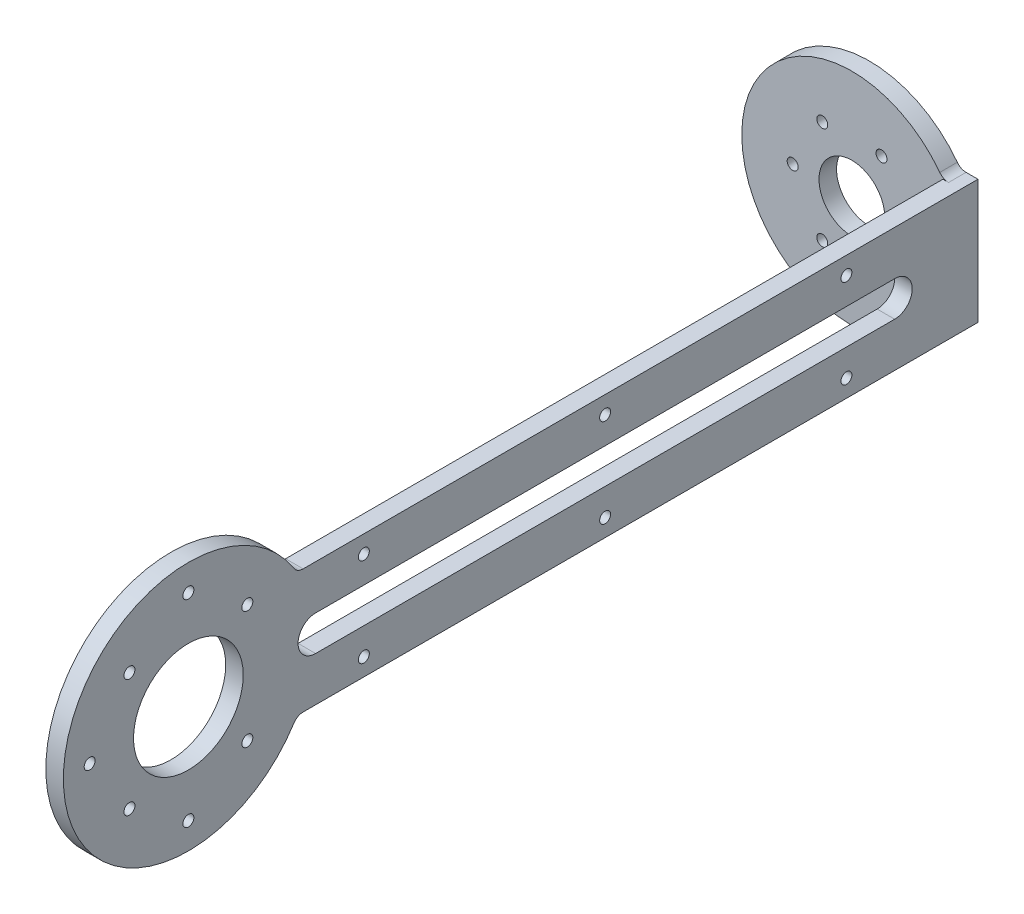
SolidWorks part; units mm, degrees
material "AISI 304"
ref_plane "前视基准面" through (0, 0, 0) normal (0, 0, 1) x (1, 0, 0)
ref_plane "上视基准面" through (0, 0, 0) normal (0, 1, 0) x (1, 0, 0)
ref_plane "右视基准面" through (0, 0, 0) normal (1, 0, 0) x (0, 0, -1)
other "Configuration Table"
sketch "草图1" plane through (0, 0, 0) normal (0, 0, 1) x (1, 0, 0)
  circle A0 centre (0, 0) radius 28.5
  dimension "D1" = 57
extrude "凸台-拉伸1" add sketch "草图1" along normal blind 4
sketch "草图2" plane through (0, 0, 4) normal (0, 0, 1) x (1, 0, 0)
  circle A0 centre (-13.5, 0) radius 1.25
  circle A1 centre (-6.75, 11.6913) radius 1.25
  circle A2 centre (6.75, 11.6913) radius 1.25
  circle A4 centre (6.75, -11.6913) radius 1.25
  circle A5 centre (-6.75, -11.6913) radius 1.25
  circle A6 centre (13.5, 0) radius 1.25 [skipped]
  point P16 (0, 0)
  dimension "D1" = 2.5
  dimension "D2" = 13.5
  dimension "D3" = 6
extrude "切除-拉伸2" cut sketch "草图2" against normal blind 4
sketch "草图4" plane through (0, 0, 4) normal (0, 0, 1) x (1, 0, 0)
  line L0 (-23.5601, 0) -> (35.9278, 0) construction
  line L1 (20.75, 14.1311) -> (20.75, -14.1311)
  line L2 (24.75, 14.1311) -> (24.75, -14.1311)
  line L3 (24.75, 14.1311) -> (20.75, 14.1311)
  line L4 (24.75, -14.1311) -> (20.75, -14.1311)
  circle A0 centre (0, 0) radius 28.5 construction
  circle A1 centre (6.75, 11.6913) radius 1.25 construction
  circle A2 centre (0, 0) radius 28.5
  circle A3 centre (6.75, 11.6913) radius 1.25
  arc A4 (20.75, 14.1311) -> (20.75, -14.1311) centre (0, 0) ccw
  circle M13 centre (0, 0) radius 28.5
  dimension "D1" = 14
  dimension "D2" = 4
extrude "切除-拉伸4" cut sketch "草图4" against normal blind 4 contours A4 L3 L4 M13 | L2 L0 A2 | L0 L2 M13 region at (26.2588, 5.349, 4) region at (26.2588, -5.349, 4) region at (-25.8848, 0, 4)
sketch "草图5" plane through (0, 0, 4) normal (0, 0, 1) x (1, 0, 0)
  circle A0 centre (0, 0) radius 7.5
  dimension "D1" = 15
extrude "切除-拉伸5" cut sketch "草图5" against normal blind 4
sketch "草图6" plane through (0, 0, 4) normal (0, 0, 1) x (1, 0, 0)
  line L0 (-22.1913, 0) -> (33.046, 0) construction
  line L1 (20.75, 14.1311) -> (24.75, 14.1311)
  line L2 (24.75, 14.1311) -> (24.75, -14.1311)
  line L3 (24.75, -14.1311) -> (20.75, -14.1311)
  line L4 (20.75, -14.1311) -> (20.75, 14.1311)
extrude "凸台-拉伸2" add sketch "草图6" along normal blind 140
sketch "草图7" plane through (24.75, 0, 0) normal (1, 0, 0) x (0, 0, -1)
  line L0 (22.302, 0) -> (-193.5409, 0) construction
  line L1 (0, 14.1311) -> (0, -14.1311) construction
  line L2 (-144, 14.1311) -> (-155.25, 14.1311)
  line L3 (-144, -14.1311) -> (-155.25, -14.1311)
  line L4 (-144, 14.1311) -> (-144, -14.1311)
  arc A0 (-155.25, 14.1311) -> (-155.25, -14.1311) centre (-180, 0) ccw
  circle A1 centre (-180, 0) radius 12.5
  dimension "D2" = 57
  dimension "D3" = 25
  dimension "D1" = 180
extrude "凸台-拉伸3" add sketch "草图7" against normal blind 4
sketch "草图8" plane through (24.75, 0, 0) normal (1, 0, 0) x (0, 0, -1)
  line L0 (22.7262, 0) -> (-180, 0) construction
  line L1 (-180, 0) -> (-128.701, 51.299) construction
  circle A0 centre (-166.565, 13.435) radius 1.25
  circle A1 centre (-166.565, -13.435) radius 1.25
  circle A2 centre (-193.435, -13.435) radius 1.25
  circle A3 centre (-193.435, 13.435) radius 1.25
  point P15 (-180, 0)
  dimension "D2" = 2.5
  dimension "D1" = 45
  dimension "D3" = 19
  dimension "D4" = 4
extrude "切除-拉伸6" cut sketch "草图8" against normal blind 4
sketch "草图9" plane through (24.75, 0, 0) normal (1, 0, 0) x (0, 0, -1)
  line L0 (24.7485, 0) -> (-180, 0) construction
  line L1 (0, 14.1311) -> (-155.25, 14.1311) construction
  line L2 (-180, 46.135) -> (-180, -30.5103) construction
  line L3 (0, 14.1311) -> (0, -14.1311) construction
  line L4 (-155, 4) -> (-15, 4)
  line L5 (-155, 4) -> (-155, -4)
  line L6 (-155, -4) -> (-15, -4)
  line L7 (-15, 4) -> (-15, -4)
  line L8 (-155, 4) -> (-15, -4) construction
  line L9 (-155, -4) -> (-15, 4) construction
  circle A0 centre (-140, 10.1311) radius 1.25
  circle A1 centre (-180, 22.5) radius 1.25
  circle A2 centre (-202.5, 0) radius 1.25
  circle A3 centre (-180, -22.5) radius 1.25
  circle A4 centre (-85, 10.1311) radius 1.25
  circle A5 centre (-30, 10.1311) radius 1.25
  circle A6 centre (-30, -10.1311) radius 1.25
  circle A7 centre (-85, -10.1311) radius 1.25
  circle A8 centre (-140, -10.1311) radius 1.25
  point P18 (-180, 0)
  point P27 (-85, 0)
  dimension "D1" = 2.5
  dimension "D3" = 40
  dimension "D4" = 2.5
  dimension "D2" = 4
  dimension "D5" = 22.5
  dimension "D8" = 4
  dimension "D9" = 140
  dimension "D10" = 85
  dimension "D7" = 3
  dimension "D6" = 3
extrude "切除-拉伸7" cut sketch "草图9" against normal blind 4
fillet "圆角1" 2 edges at (22.75, 4, 155) (22.75, -4, 155) type full round first side face at (22.75, 4, 85) second side face at (22.75, -4, 85) middle face at (22.75, 0, 155)
fillet "圆角2" 2 edges at (22.75, 4, 15) (22.75, -4, 15) type full round first side face at (22.75, 4, 83) second side face at (22.75, -4, 83) middle face at (22.75, 0, 15)
fillet "圆角3" radius 2.5 4 edges at (22.75, -14.1311, 155.25) (22.75, 14.1311, 155.25) (20.75, -14.1311, 2) (20.75, 14.1311, 2)
